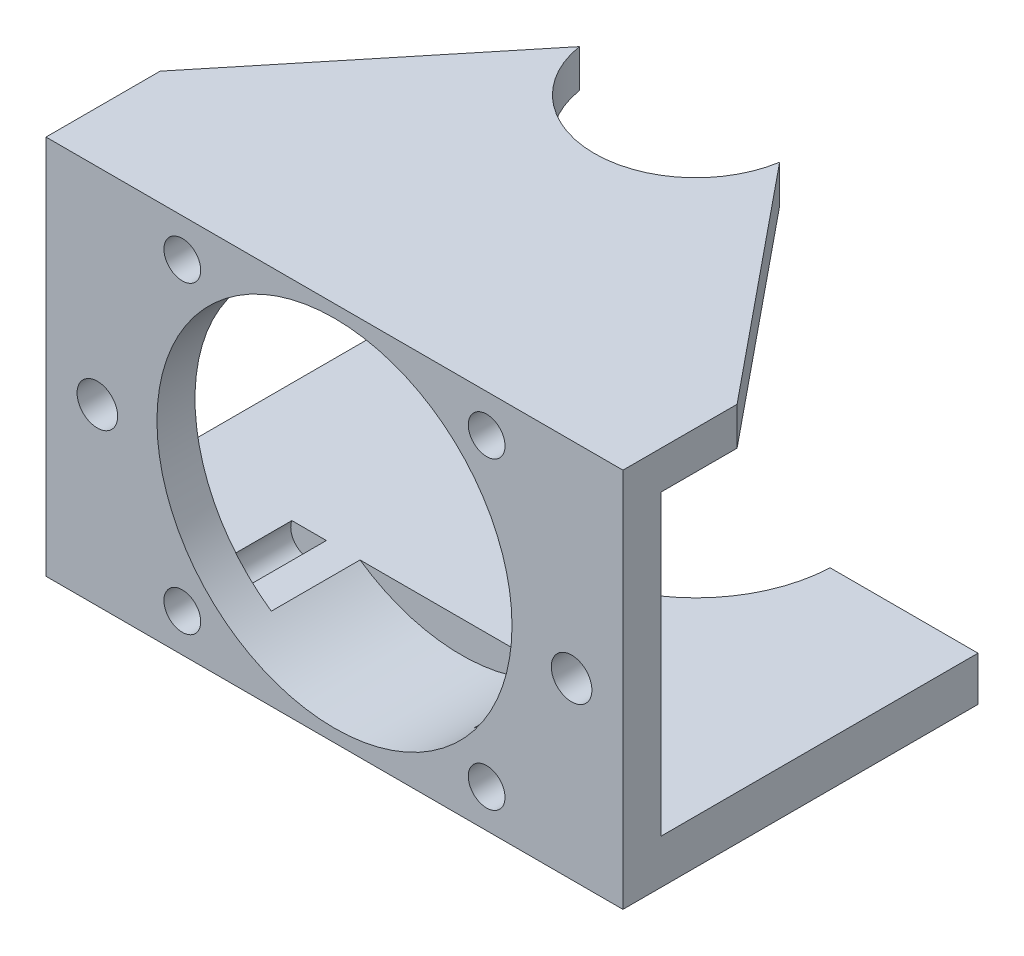
SolidWorks part; units mm, degrees
ref_plane "Front Plane" through (0, 0, 0) normal (0, 0, 1) x (1, 0, 0)
ref_plane "Top Plane" through (0, 0, 0) normal (0, 1, 0) x (1, 0, 0)
ref_plane "Right Plane" through (0, 0, 0) normal (1, 0, 0) x (0, 0, -1)
sketch "Sketch1" plane through (0, 0, 0) normal (0, 0, 1) x (1, 0, 0)
  line L1 (0, 0) -> (45.5, 0)
  line L2 (0, 0) -> (0, 30)
  line L3 (0, 30) -> (45.5, 30)
  line L4 (45.5, 0) -> (45.5, 30)
  dimension "D1" = 45.5
  dimension "D2" = 30
extrude "Boss-Extrude1" add sketch "Sketch1" along normal blind 28
sketch "Sketch2" plane through (0, 30, 0) normal (0, 1, 0) x (1, 0, 0)
  line L1 (22.75, -28) -> (22.75, 0) construction
  line L2 (45.5, -28) -> (0, -28) construction
  line L3 (45.5, 0) -> (0, 0) construction
  circle A0 centre (22.75, 0.5) radius 8
  point P8 (0, 0)
  point P9 (22.75, -3.1536)
  dimension "D1" = 16
  dimension "D2" = 0.5
extrude "Cut-Extrude1" cut sketch "Sketch2" against normal blind 30
sketch "Sketch3" plane through (0, 0, 0) normal (0, -1, 0) x (1, 0, 0)
  circle A0 centre (22.75, -0.5) radius 11.1
  dimension "D1" = 22.2
extrude "Cut-Extrude2" cut sketch "Sketch3" against normal offset from surface (27 mm away) 3 up to face at (22.75, 30, 10.5833)
sketch "Sketch4" plane through (45.5, 0, 0) normal (1, 0, 0) x (0, 0, -1)
  line L0 (0, 0) -> (0, 30) construction
  line L1 (0, 27) -> (-25, 27)
  line L2 (0, 27) -> (0, 3.5)
  line L3 (0, 3.5) -> (-25, 3.5)
  line L4 (-25, 27) -> (-25, 3.5)
  line L6 (-28, 0) -> (0, 0) construction
  dimension "D1" = 3.5
  dimension "D2" = 25
  dimension "D3" = 23.5
extrude "Cut-Extrude3" cut sketch "Sketch4" against normal through all
sketch "Sketch5" plane through (0, 30, 0) normal (0, 1, 0) x (1, 0, 0)
  line L0 (0, -19) -> (15.5, 0)
  line L1 (0, -28) -> (0, 0) construction
  line L2 (15.5, 0) -> (0, 0)
  line L3 (0, 0) -> (0, -19)
  line L4 (30, 0) -> (45.5, -19)
  line L5 (45.5, -28) -> (45.5, 0) construction
  line L6 (45.5, -19) -> (45.5, 0)
  line L7 (45.5, 0) -> (30.7344, 0) construction
  line L8 (45.5, 0) -> (30, 0)
  line L9 (45.5, 0) -> (30.7344, 0) construction
  line L10 (14.7656, 0) -> (0, 0) construction
  point P12 (0, 0)
  point P16 (30.4724, 0)
  point P17 (31.5195, 0)
  point P20 (12.9334, 0)
  dimension "D1" = 15.5
  dimension "D2" = 15.5
  dimension "D3" = 19
  dimension "D4" = 19
extrude "Cut-Extrude4" cut sketch "Sketch5" against normal blind 10
sketch "Sketch7" plane through (0, 0, 28) normal (0, 0, 1) x (1, 0, 0)
  line L0 (0, 30) -> (0, 0) construction
  line L1 (45.5, 0) -> (45.5, 30) construction
  line L2 (0, 0) -> (45.5, 0) construction
  circle A0 centre (4.05, 13.75) radius 1.6
  circle A1 centre (41.45, 13.75) radius 1.6
  point P10 (0, 0)
  point P11 (0, 0)
  dimension "D1" = 3.2
  dimension "D2" = 4.05
  dimension "D3" = 4.05
  dimension "D4" = 13.75
extrude "Cut-Extrude5" cut sketch "Sketch7" against normal blind 10
sketch "Sketch8" plane through (0, 0, 28) normal (0, 0, 1) x (1, 0, 0)
  circle A0 centre (22.75, 15) radius 14
  circle A1 centre (10.75, 27) radius 1.45
  circle A2 centre (34.75, 27) radius 1.45
  circle A3 centre (34.75, 3) radius 1.45
  circle A4 centre (10.75, 3) radius 1.45
  dimension "D1" = 28
  dimension "D2" = 2.9
extrude "Cut-Extrude6" cut sketch "Sketch8" against normal blind 10
